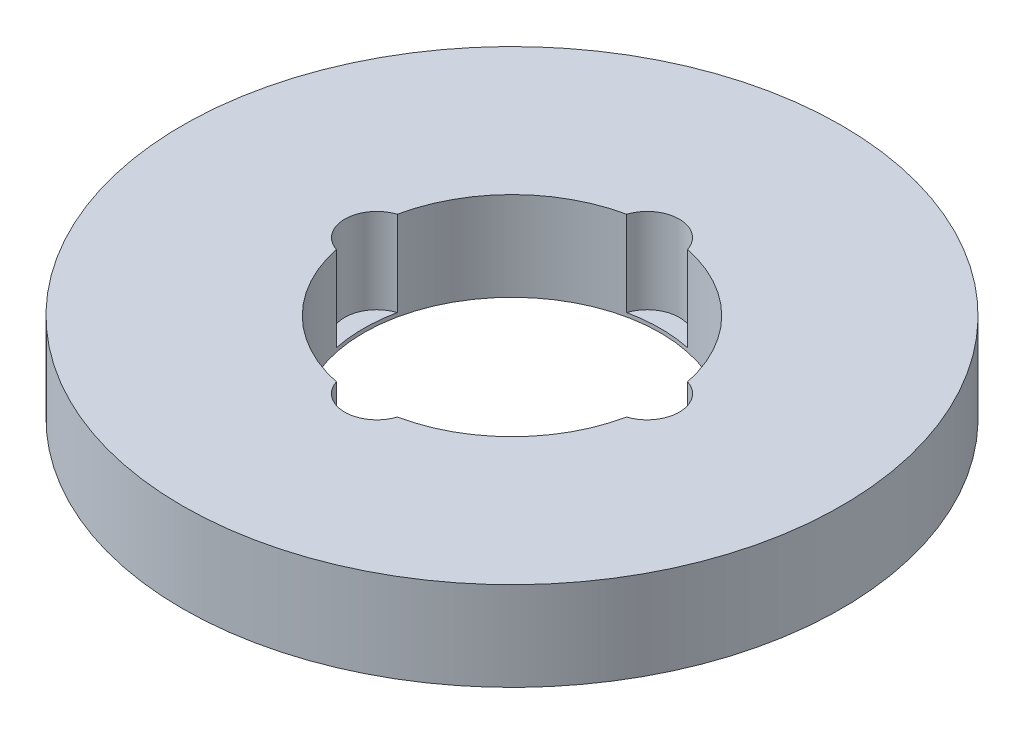
SolidWorks part; units mm, degrees
ref_plane "Front Plane" through (0, 0, 0) normal (0, 0, 1) x (1, 0, 0)
ref_plane "Top Plane" through (0, 0, 0) normal (0, 1, 0) x (1, 0, 0)
ref_plane "Right Plane" through (0, 0, 0) normal (1, 0, 0) x (0, 0, -1)
sketch "Sketch1" plane through (0, 0, 0) normal (0, 1, 0) x (1, 0, 0)
  circle A0 centre (0, 0) radius 100
  dimension "FLANGE_OD" = 200
extrude "Boss-Extrude1" add sketch "Sketch1" along normal blind 27
sketch "Sketch2" plane through (0, 0, 0) normal (0, 1, 0) x (1, 0, 0)
  circle A0 centre (0, 0) radius 45
  dimension "BORE_D" = 90
extrude "Cut-Extrude1" cut sketch "Sketch2" along normal through all
sketch "Sketch3" plane through (0, 27, 0) normal (0, 1, 0) x (1, 0, 0)
  circle A0 centre (0, 0) radius 41.0077 construction
  circle A1 centre (-41.0077, 0) radius 9.7413
  dimension "BOLT_D" = 19.4825
  dimension "BOLT_PCD" = 82.0154
extrude "Cut-Extrude2" cut sketch "Sketch3" against normal blind 25.8376
pattern_circular "CirPattern1" count 4 over 360 about axis through (0, 0, 0) along (0, 1, 0) of "Cut-Extrude2"
